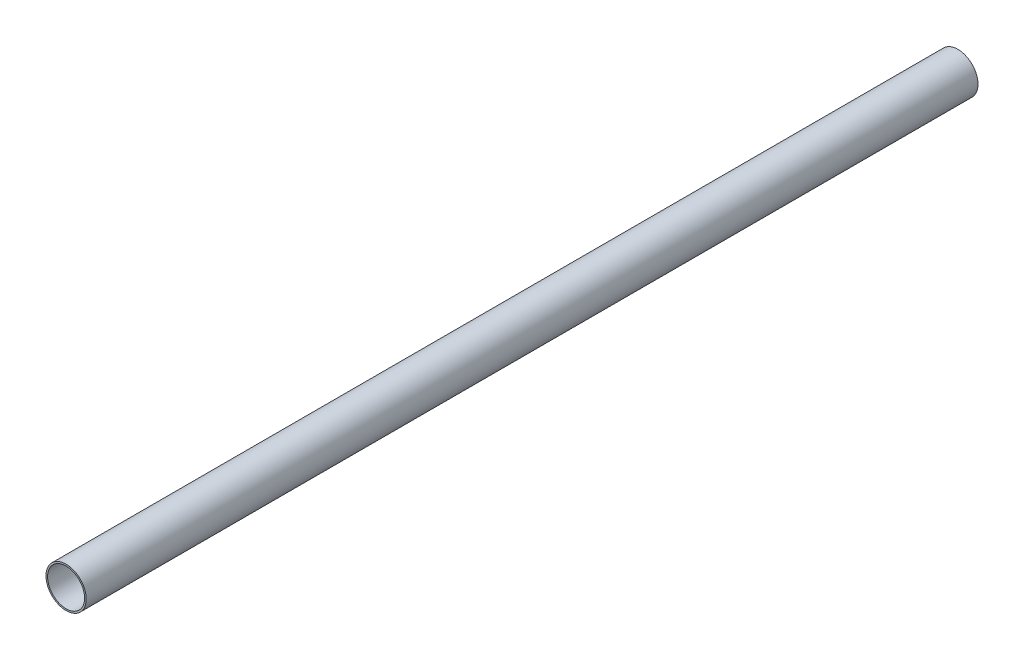
SolidWorks part; units mm, degrees
ref_plane "Front Plane" through (0, 0, 0) normal (0, 0, 1) x (1, 0, 0)
ref_plane "Top Plane" through (0, 0, 0) normal (0, 1, 0) x (1, 0, 0)
ref_plane "Right Plane" through (0, 0, 0) normal (1, 0, 0) x (0, 0, -1)
sketch "Sketch1" plane through (0, 0, 0) normal (0, 0, 1) x (1, 0, 0)
  circle A0 centre (0, 0) radius 12.5
  circle A1 centre (0, 0) radius 11.5
  dimension "D1" = 25
  dimension "D2" = 1
extrude "Boss-Extrude1" add sketch "Sketch1" along normal blind 553.63
